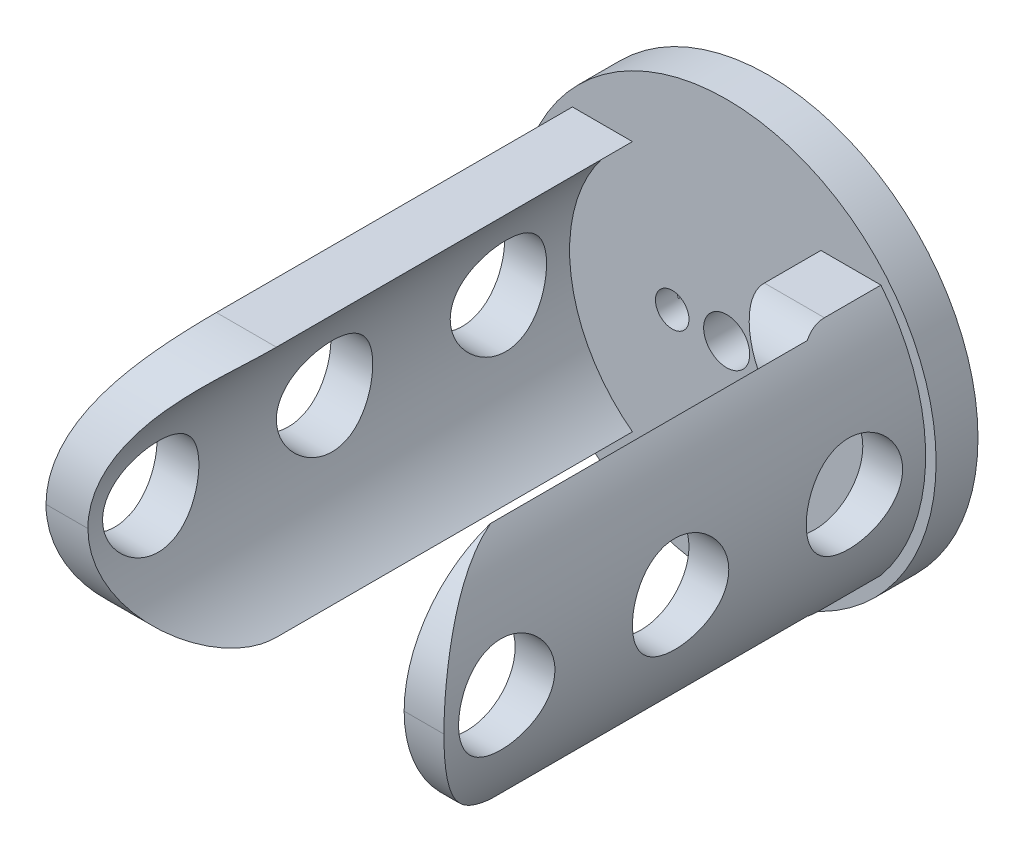
SolidWorks part; units mm, degrees
material "ABS"
ref_plane "Plan de face" through (0, 0, 0) normal (0, 0, 1) x (1, 0, 0)
ref_plane "Plan de dessus" through (0, 0, 0) normal (0, 1, 0) x (1, 0, 0)
ref_plane "Plan de droite" through (0, 0, 0) normal (1, 0, 0) x (0, 0, -1)
sketch "Esquisse1" plane through (0, 0, 0) normal (0, 0, 1) x (1, 0, 0)
  circle A0 centre (0, 0) radius 50
  dimension "D1" = 100
extrude "Boss.-Extru.1" add sketch "Esquisse1" along normal blind 10
sketch "Esquisse2" plane through (0, 0, 0) normal (0, 0, -1) x (-1, 0, 0)
  circle A0 centre (0, 0) radius 47.5
  dimension "D1" = 95
extrude "Enlèv. mat.-Extru.1" cut sketch "Esquisse2" against normal blind 5
sketch "Esquisse6" plane through (0, 0, 10) normal (0, 0, 1) x (1, 0, 0)
  line L0 (0, 0) -> (0, 47.5) construction
  line L1 (0, 47.5) -> (0, -47.5) construction
  line L2 (-22.5, 30) -> (-22.5, -30) construction
  line L3 (-22.5, 30) -> (-36.8273, 30)
  line L4 (-22.5, -30) -> (-36.8273, -30)
  line L5 (22.5, -30) -> (36.8273, -30)
  line L6 (22.5, 30) -> (36.8273, 30)
  circle A0 centre (0, 0) radius 2
  circle A1 centre (0, 0) radius 47.5
  circle A2 centre (0, 0) radius 37.5
  circle A3 centre (0, 0) radius 50 construction
  dimension "D1" = 4
  dimension "D2" = 2.5
  dimension "D3" = 10
  dimension "D4" = 60
extrude "Boss.-Extru.4" add sketch "Esquisse6" along normal blind 115 contours A2 L3 A1 L4 | A2 L5 A1 L6 region at (-38.1648, 0, 10) region at (38.1648, 0, 10)
sketch "Esquisse7" plane through (0, 0, 5) normal (0, 0, -1) x (-1, 0, 0)
  circle A0 centre (0, 0) radius 5.5
  dimension "D1" = 11
extrude "Enlèv. mat.-Extru.2" cut sketch "Esquisse7" against normal blind 100
sketch "Esquisse12" plane through (0, 0, 10) normal (0, 0, 1) x (1, 0, 0)
  line L1 (-3.6437, 25.162) -> (0, 25.162)
  line L2 (-3.6437, 25.162) -> (-3.6437, 15.1247)
  line L3 (-3.6437, 15.1247) -> (0, 15.1247)
  line L4 (0, 25.162) -> (0, 15.1247)
extrude "Boss.-Extru.7" add sketch "Esquisse12" along normal blind 116
sketch "Esquisse14" plane through (0, 0, 0) normal (1, 0, 0) x (0, 0, -1)
  line L0 (-125, 0) -> (-10, 0) construction
  line L1 (-125, 30) -> (-125, -30) construction
  line L2 (-10, 50) -> (-10, -50) construction
  circle A0 centre (-110, 0) radius 11.5
  circle A2 centre (-68.5, 0) radius 11.5
  circle A3 centre (-27, 0) radius 11.5
  dimension "D4" = 23
  dimension "D5" = 23
  dimension "D6" = 23
  dimension "D1" = 100
  dimension "D2" = 17
  dimension "D3" = 41.5
extrude "Enlèv. mat.-Extru.3" cut sketch "Esquisse14" against normal through all both and the other way through all
sketch "Esquisse15" plane through (0, 0, 126) normal (0, 0, 1) x (1, 0, 0)
  line L1 (0, 15.1247) -> (-3.6437, 15.1247)
  line L2 (0, 15.1247) -> (0, 25.162)
  line L3 (0, 25.162) -> (-3.6437, 25.162)
  line L4 (-3.6437, 15.1247) -> (-3.6437, 25.162)
extrude "Enlèv. mat.-Extru.4" cut sketch "Esquisse15" against normal blind 116
sketch "Esquisse16" plane through (0, 0, 5) normal (0, 0, -1) x (-1, 0, 0)
  circle A0 centre (0, 0) radius 20
  circle A1 centre (0, 0) radius 2
  dimension "D1" = 40
extrude "Boss.-Extru.8" add sketch "Esquisse16" along normal blind 16
sketch "Esquisse17" plane through (0, 0, -11) normal (0, 0, -1) x (-1, 0, 0)
  line L0 (0, 0) -> (0, 20) construction
  line L1 (0, 20) -> (0, -20) construction
  line L2 (0, 0) -> (20, 0) construction
  line L3 (20, 0) -> (-20, 0) construction
  line L4 (0, 20) -> (1.98, 14.8687)
  line L5 (0, 20) -> (-1.98, 14.8687)
  line L6 (-0.9649, 14.9689) -> (-3.9011, 19.6158)
  line L7 (-3.9011, 19.6158) -> (-4.8485, 14.1948)
  line L8 (-3.9011, 19.6158) -> (0, 0) construction
  line L9 (0, 0) -> (3.9011, -19.6158) construction
  line L10 (-7.6524, 18.4781) -> (0, 0) construction
  line L11 (-11.1097, 16.6305) -> (0, 0) construction
  line L12 (-14.1402, 14.1441) -> (0, 0) construction
  line L13 (0, 0) -> (-16.6275, 11.1143) construction
  line L14 (0, 0) -> (-18.476, 7.6575) construction
  line L15 (0, 0) -> (-19.6148, 3.9065) construction
  line L16 (-9.9008, 11.2683) -> (-11.1097, 16.6305)
  line L17 (-11.1097, 16.6305) -> (-6.6069, 13.4666)
  line L18 (-11.2656, 9.9039) -> (-16.6275, 11.1143)
  line L19 (-16.6275, 11.1143) -> (-13.4647, 6.6107)
  line L20 (-14.9687, 0.9691) -> (-19.6148, 3.9065)
  line L21 (-19.6148, 3.9065) -> (-14.1934, 4.8524)
  line L22 (-7.6524, 18.4781) -> (-3.8597, 14.4949)
  line L23 (-7.6524, 18.4781) -> (-7.5184, 12.9797)
  line L24 (-14.1402, 14.1441) -> (-9.1121, 11.9151)
  line L25 (-14.1402, 14.1441) -> (-11.9126, 9.1154)
  line L26 (-18.476, 7.6575) -> (-14.4938, 3.8637)
  line L27 (-18.476, 7.6575) -> (-12.9777, 7.522)
  line L28 (-20, 0) -> (-14.8675, 1.9891)
  line L29 (-20, 0) -> (-14.8675, -1.9891)
  line L30 (-14.9687, -0.9691) -> (-19.6148, -3.9065)
  line L31 (-19.6148, -3.9065) -> (-14.1934, -4.8524)
  line L32 (-18.476, -7.6575) -> (-14.4938, -3.8637)
  line L33 (-18.476, -7.6575) -> (-12.9777, -7.522)
  line L34 (-16.6275, -11.1143) -> (-13.4647, -6.6107)
  line L35 (-11.2656, -9.9039) -> (-16.6275, -11.1143)
  line L36 (-14.1402, -14.1441) -> (-11.9126, -9.1154)
  line L37 (-14.1402, -14.1441) -> (-9.1121, -11.9151)
  line L38 (-9.9008, -11.2683) -> (-11.1097, -16.6305)
  line L39 (-11.1097, -16.6305) -> (-6.6069, -13.4666)
  line L40 (-7.6524, -18.4781) -> (-7.5184, -12.9797)
  line L41 (-7.6524, -18.4781) -> (-3.8597, -14.4949)
  line L42 (-3.9011, -19.6158) -> (-4.8485, -14.1948)
  line L43 (-0.9649, -14.9689) -> (-3.9011, -19.6158)
  line L44 (0, -20) -> (-1.98, -14.8687)
  line L45 (0, -20) -> (1.98, -14.8687)
  line L46 (0.9649, -14.9689) -> (3.9011, -19.6158)
  line L47 (3.9011, -19.6158) -> (4.8485, -14.1948)
  line L48 (7.6524, -18.4781) -> (3.8597, -14.4949)
  line L49 (7.6524, -18.4781) -> (7.5184, -12.9797)
  line L50 (11.1097, -16.6305) -> (6.6069, -13.4666)
  line L51 (9.9008, -11.2683) -> (11.1097, -16.6305)
  line L52 (14.1402, -14.1441) -> (9.1121, -11.9151)
  line L53 (14.1402, -14.1441) -> (11.9126, -9.1154)
  line L54 (11.2656, -9.9039) -> (16.6275, -11.1143)
  line L55 (16.6275, -11.1143) -> (13.4647, -6.6107)
  line L56 (18.476, -7.6575) -> (12.9777, -7.522)
  line L57 (18.476, -7.6575) -> (14.4938, -3.8637)
  line L58 (19.6148, -3.9065) -> (14.1934, -4.8524)
  line L59 (14.9687, -0.9691) -> (19.6148, -3.9065)
  line L60 (20, 0) -> (14.8675, -1.9891)
  line L61 (20, 0) -> (14.8675, 1.9891)
  line L62 (14.9687, 0.9691) -> (19.6148, 3.9065)
  line L63 (19.6148, 3.9065) -> (14.1934, 4.8524)
  line L64 (18.476, 7.6575) -> (14.4938, 3.8637)
  line L65 (18.476, 7.6575) -> (12.9777, 7.522)
  line L66 (16.6275, 11.1143) -> (13.4647, 6.6107)
  line L67 (11.2656, 9.9039) -> (16.6275, 11.1143)
  line L68 (14.1402, 14.1441) -> (11.9126, 9.1154)
  line L69 (14.1402, 14.1441) -> (9.1121, 11.9151)
  line L70 (9.9008, 11.2683) -> (11.1097, 16.6305)
  line L71 (11.1097, 16.6305) -> (6.6069, 13.4666)
  line L72 (7.6524, 18.4781) -> (7.5184, 12.9797)
  line L73 (7.6524, 18.4781) -> (3.8597, 14.4949)
  line L74 (3.9011, 19.6158) -> (4.8485, 14.1948)
  line L75 (0.9649, 14.9689) -> (3.9011, 19.6158)
  line L76 (0, 20) -> (1.98, 14.8687)
  circle A0 centre (0, 0) radius 20
  circle A1 centre (0, 0) radius 2
  circle A2 centre (0, 0) radius 15
  circle M45 centre (0, 0) radius 20
  dimension "D4" = 1.98
  dimension "D5" = 3.96
  dimension "D6" = 1.02
  dimension "D8" = 1.02
extrude "Enlèv. mat.-Extru.7" cut sketch "Esquisse17" against normal blind 16 contours L30 L29 M45 | L32 L31 M45 | L34 L33 M45 | L36 L35 M45 | L38 L37 M45 | L40 L39 M45 | L42 L41 M45 | L44 L43 M45 | L46 L45 M45 | L48 L47 M45 | L50 L49 M45 | L52 L51 M45 | L54 L53 M45 | L56 L55 M45 | L58 L57 M45 | L60 L59 M45 | L62 L61 M45 | L64 L63 M45 | L66 L65 M45 | L68 L67 M45 | L70 L69 M45 | L72 L71 M45 | L74 L73 M45 | L4 L75 M45 | L6 L5 M45 | L22 L7 M45 | L23 L17 M45 | L24 L16 M45 | L25 L18 M45 | L27 L19 M45 | L26 L21 M45 | L28 L20 M45 region at (-1.8282, 18.5572, -11) region at (1.8282, 18.5572, -11) region at (-5.4138, 17.8474, -11) region at (5.4138, 17.8474, -11) region at (-8.7896, 16.4494, -11) region at (8.7896, 16.4494, -11) region at (-11.8272, 14.4163, -11) region at (11.8272, 14.4163, -11) region at (-14.413, 11.8311, -11) region at (14.413, 11.8311, -11) region at (-16.447, 8.7941, -11) region at (16.447, 8.7941, -11) region at (-17.8459, 5.4187, -11) region at (17.8459, 5.4187, -11) region at (-18.5577, 1.832, -11) region at (18.5577, 1.832, -11) region at (-18.5577, -1.832, -11) region at (18.5577, -1.832, -11) region at (-17.8459, -5.4187, -11) region at (17.8459, -5.4187, -11) region at (-16.447, -8.7941, -11) region at (16.447, -8.7941, -11) region at (-14.413, -11.8311, -11) region at (14.413, -11.8311, -11) region at (-11.8272, -14.4163, -11) region at (11.8272, -14.4163, -11) region at (-8.7896, -16.4494, -11) region at (8.7896, -16.4494, -11) region at (-5.4138, -17.8474, -11) region at (5.4138, -17.8474, -11) region at (-1.8282, -18.5572, -11) region at (1.8282, -18.5572, -11)
fillet "Congé3" radius 30 4 edges at (29.6636, -30, 125) (-29.6636, -30, 125) (-29.6636, 30, 125) (29.6636, 30, 125)
sketch "Esquisse18" plane through (0, 0, 10) normal (0, 0, 1) x (1, 0, 0)
  line L0 (35, 0) -> (35, 35.7071)
  line L1 (35, 35.7071) -> (35, -35.7071)
  line L2 (35, -15) -> (37, -15)
  line L3 (35, 35.7071) -> (32, 35.7071)
  line L4 (35, 35.7071) -> (35, -35.7071)
  line L5 (35, -35.7071) -> (32, -35.7071)
  line L6 (32, 35.7071) -> (32, -35.7071)
  line L7 (35, 35.7071) -> (37, 35.7071)
  line L8 (35, 35.7071) -> (35, -35.7071)
  line L9 (35, -35.7071) -> (37, -35.7071)
  line L10 (37, 35.7071) -> (37, -35.7071)
  line L11 (35, 0) -> (37, 0)
  line L12 (35, 0) -> (35, 15)
  line L13 (35, 15) -> (37, 15)
  line L14 (37, 0) -> (37, 15)
  line L15 (37, 0) -> (32, 0)
  line L16 (32, 0) -> (34.5, 0)
  line L18 (38, -17) -> (31, -17)
  line L19 (38, -17) -> (38, 17)
  line L20 (38, 17) -> (31, 17)
  line L21 (31, -17) -> (31, 17)
  line L22 (38, -17) -> (31, 17) construction
  line L23 (38, 17) -> (31, -17) construction
  circle A0 centre (0, 0) radius 35
  circle A1 centre (0, 0) radius 50 construction
  arc M17 (22.5, -30) -> (22.5, 30) centre (0, 0) ccw
  dimension "D1" = 70
  dimension "D2" = 3
  dimension "D3" = 2
  dimension "D4" = 15
  dimension "D5" = 2.5
  dimension "D6" = 1
  dimension "D7" = 2
extrude "Enlèv. mat.-Extru.8" cut sketch "Esquisse18" along normal blind 150 contours L19 L20 L10 L18 M17 | L0 L11 L10 M17 | L13 L0 L10 M17 | L10 L20 L8 L13 | L11 L1 L10 M17 | L10 L1 L2 M17 | L18 L10 L2 L1 | L8 L20 L0 M17 | L18 L1 M17 region at (35.8843, -5.3474, 10) region at (35.8843, 5.3474, 10) region at (34.487, 15.8492, 10) region at (36.2519, 12.1846, 10) region at (36.2519, -12.1846, 10) region at (34.487, -15.8492, 10) region at (36, 16, 10) region at (37.5408, 0, 10) region at (36, -16, 10)
sketch "Esquisse21" plane through (38, 0, 0) normal (-1, 0, 0) x (0, 0, 1)
  line L0 (68.5, 0) -> (33.5, 0) construction
  line L1 (95, 30) -> (10, 30) construction
  line L2 (33.5, 30) -> (125, 30)
  line L3 (33.5, 30) -> (33.5, 0)
  line L4 (33.5, 0) -> (125, 0)
  line L5 (125, 30) -> (125, 0)
  line L7 (33.5, 0) -> (95, 0)
  line L8 (33.5, 0) -> (33.5, -30)
  line L9 (33.5, -30) -> (95, -30)
  line L10 (95, 0) -> (95, -30)
  line L11 (95, 0) -> (125, 0)
  line L12 (95, 0) -> (95, -30)
  line L13 (95, -30) -> (125, -30)
  line L14 (125, 0) -> (125, -30)
  line M2 (119.7184, 17) -> (10, 17)
  line M4 (10, -17) -> (119.7184, -17)
  arc M5 (119.7184, -17) -> (125, 0) centre (95, 0) ccw
  arc M6 (125, 0) -> (119.7184, 17) centre (95, 0) ccw
  circle M7 centre (110, 0) radius 11.5
  circle M8 centre (68.5, 0) radius 11.5
  circle M9 centre (27, 0) radius 11.5
  dimension "D1" = 35
extrude "Enlèv. mat.-Extru.9" cut sketch "Esquisse21" along normal blind 20 contours L5 L2 L3 M2 M6 | L4 L3 M9 M8 M7 M6 M2 | L10 L4 L8 M8 M9 M4 | L4 L10 M4 M5 M7 | L10 L8 L9 M4 | L14 L10 L13 M5 M4 region at (38, 23.2478, 80.2943) region at (38, 9.9281, 75.5662) region at (38, -8.7985, 123.3199) region at (38, -22.7664, 110.9241) region at (38, -0.6381, 47.75) region at (38, -23.5, 64.25)
fillet "Congé4" radius 10 2 edges at (29.6636, -30, 33.5) (29.6636, 30, 33.5)
sketch "Esquisse22" plane through (0, 0, -11) normal (0, 0, -1) x (-1, 0, 0)
  line L0 (0, 0) -> (20, 0) construction
  line L1 (20, 0) -> (-20, 0) construction
  line L2 (0, 20) -> (0, -20) construction
  circle A1 centre (-13, 0) radius 2.5
  circle A2 centre (13, 0) radius 2.5
  dimension "D2" = 5
  dimension "D3" = 13
extrude "Enlèv. mat.-Extru.10" cut sketch "Esquisse22" against normal blind 41
sketch "Esquisse23" plane through (0, 0, 10) normal (0, 0, 1) x (1, 0, 0)
  circle A0 centre (-13, 0) radius 4
  circle A1 centre (13, 0) radius 4
  dimension "D1" = 8
  dimension "D2" = 8
extrude "Enlèv. mat.-Extru.11" cut sketch "Esquisse23" against normal blind 11
sketch "Esquisse24" plane through (0, 0, 5) normal (0, 0, 1) x (1, 0, 0)
  circle A0 centre (0, 0) radius 5.5
extrude "Enlèv. mat.-Extru.12" cut sketch "Esquisse24" against normal blind 28
sketch "Esquisse25" plane through (0, 0, -11) normal (0, 0, -1) x (-1, 0, 0)
  line L0 (0, 17.5) -> (0, -17.5) construction
  line L1 (-17, -4) -> (-9, -4)
  line L2 (-17, -4) -> (-17, 4)
  line L3 (-17, 4) -> (-9, 4)
  line L4 (-9, -4) -> (-9, 4)
  line L5 (-17, -4) -> (-9, 4) construction
  line L6 (-17, 4) -> (-9, -4) construction
  line L7 (-17.5, 0) -> (17.5, 0) construction
  line L8 (17, 4) -> (9, 4)
  line L9 (9, -4) -> (9, 4)
  line L10 (17, -4) -> (9, -4)
  line L11 (17, -4) -> (17, 4)
  circle A0 centre (-13, 0) radius 2.5324
  circle A1 centre (13, 0) radius 2.5
  circle A2 centre (0, 0) radius 17.5
  circle A3 centre (0, 0) radius 5.5
  dimension "D1" = 35
  dimension "D2" = 8
  dimension "D4" = 11
  dimension "D3" = 8
